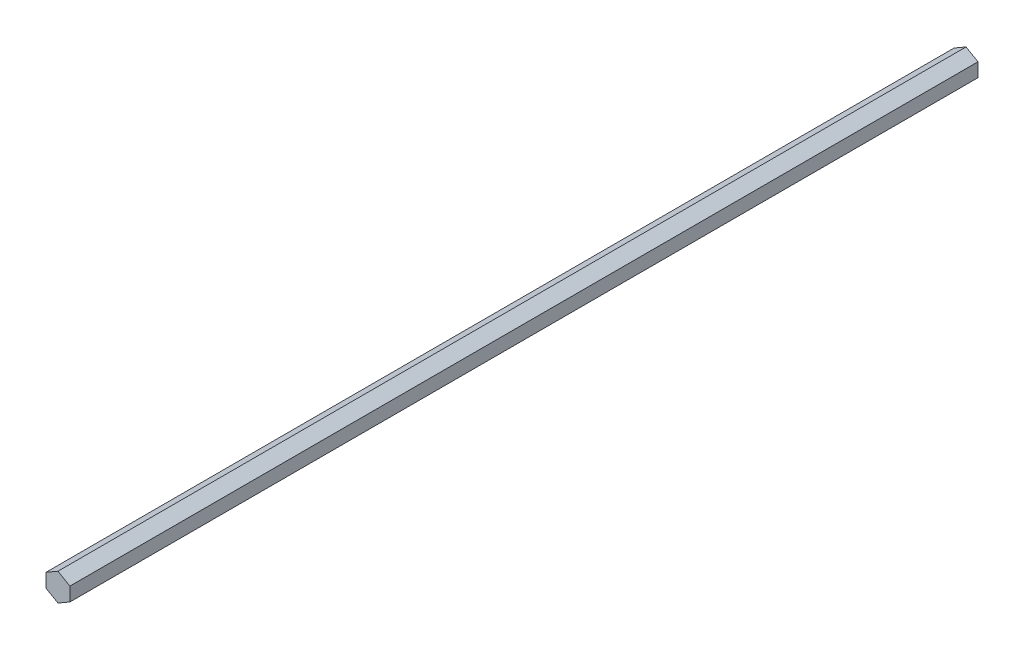
SolidWorks part; units mm, degrees
ref_plane "Front Plane" through (0, 0, 0) normal (0, 0, 1) x (1, 0, 0)
ref_plane "Top Plane" through (0, 0, 0) normal (0, 1, 0) x (1, 0, 0)
ref_plane "Right Plane" through (0, 0, 0) normal (1, 0, 0) x (0, 0, -1)
sketch "Sketch1" plane through (0, 0, 0) normal (0, 0, 1) x (1, 0, 0)
  line L0 (-6.35, 0) -> (6.35, 0) construction
  line L9 (0, 7.3323) -> (-6.35, 3.6662) construction
  line L10 (-6.35, 3.6662) -> (-6.35, -3.6662) construction
  line L11 (-6.35, -3.6662) -> (0, -7.3323) construction
  line L12 (0, -7.3323) -> (6.35, -3.6662) construction
  line L13 (6.35, -3.6662) -> (6.35, 3.6662) construction
  line L14 (6.35, 3.6662) -> (0, 7.3323) construction
  circle A3 centre (0, 0) radius 6.35 construction
  point P4 (0, 0)
  dimension "Width" = 12.7
sketch "Sketch2" plane through (0, 0, 0) normal (1, 0, 0) x (0, 0, -1)
  line L0 (241.3, 7.3323) -> (-241.3, 7.3323) construction
  point P3 (-226.695, 7.3323)
  point P4 (0, 7.3323)
  point P5 (226.695, 7.3323)
  dimension "Length" = 482.6
  dimension "D1" = 14.605
  dimension "D2" = 14.605
sketch "Sketch3" plane through (0, 0, 0) normal (0, 0, 1) x (1, 0, 0)
  line L1 (0, 7.3323) -> (6.35, 3.6662)
  line L2 (6.35, 3.6662) -> (6.35, -3.6662)
  line L3 (6.35, -3.6662) -> (0, -7.3323)
  line L4 (0, -7.3323) -> (-6.35, -3.6662)
  line L5 (-6.35, -3.6662) -> (-6.35, 3.6662)
  line L6 (-6.35, 3.6662) -> (0, 7.3323)
extrude "Boss-Extrude1" add sketch "Sketch3" along normal mid plane 482.6
equation "\"D1@Boss-Extrude1\" = \"Length@Sketch2\""
equation "\"D1@Sketch2\" = \"Width@Sketch1\" * 1.15"
equation "\"D2@Sketch2\"=\"D1@Sketch2\""
